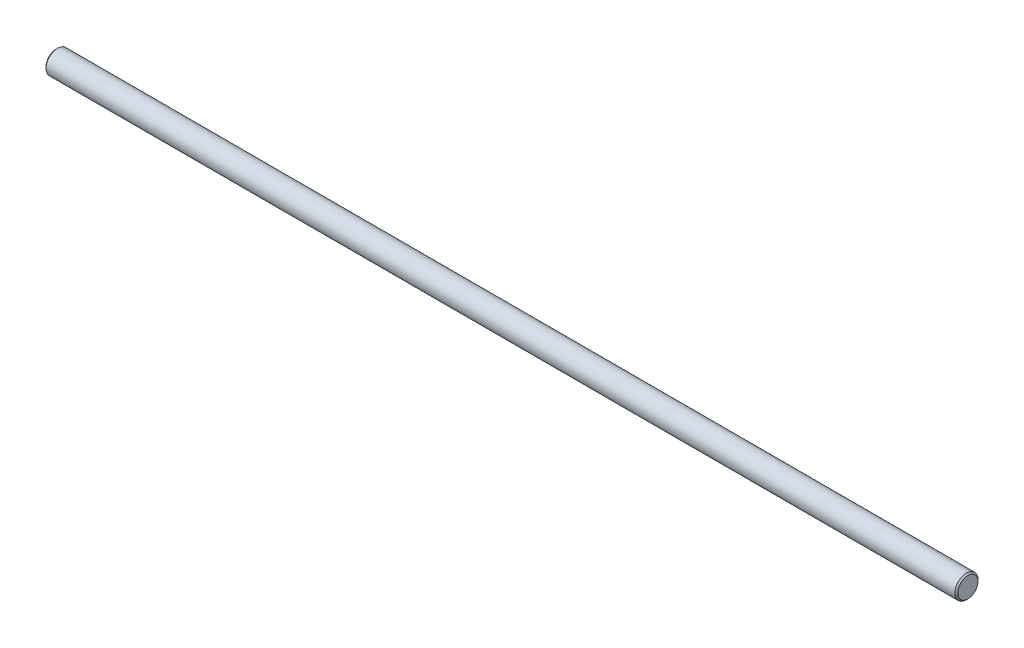
SolidWorks part; units mm, degrees
ref_plane "Front Plane" through (0, 0, 0) normal (0, 0, 1) x (1, 0, 0)
ref_plane "Top Plane" through (0, 0, 0) normal (0, 1, 0) x (1, 0, 0)
ref_plane "Right Plane" through (0, 0, 0) normal (1, 0, 0) x (0, 0, -1)
sketch "Sketch1" plane through (0, 0, 0) normal (0, 0, 1) x (1, 0, 0)
  line L0 (0, 3.5) -> (0, 0)
  line L1 (0, 0) -> (315, 0)
  line L2 (315, 0) -> (315, 3.5)
  line L3 (315, 3.5) -> (314.5, 4)
  line L4 (314.5, 4) -> (0.5, 4)
  line L5 (0.5, 4) -> (0, 3.5)
  line L6 (0, 0) -> (315, 0) construction
revolve "Revolve1" add sketch "Sketch1" angle 360 about L6 reverse direction yes
